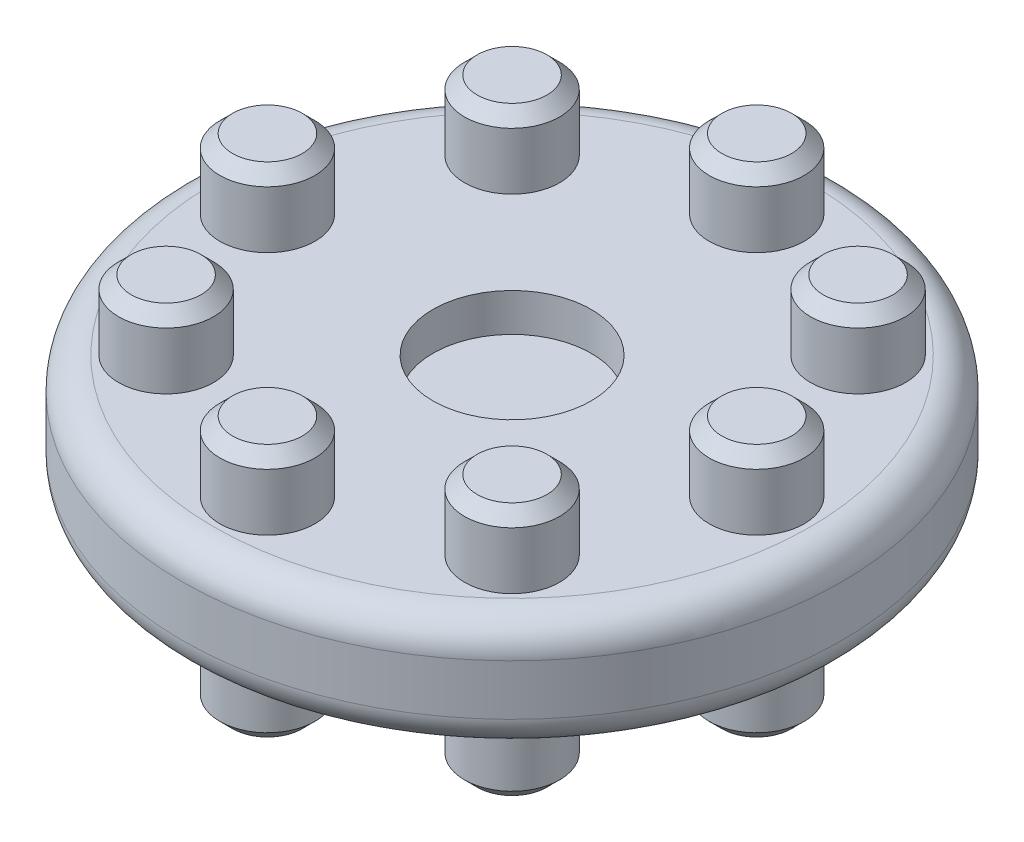
SolidWorks part; units mm, degrees
ref_plane "Front Plane" through (0, 0, 0) normal (0, 0, 1) x (1, 0, 0)
ref_plane "Top Plane" through (0, 0, 0) normal (0, 1, 0) x (1, 0, 0)
ref_plane "Right Plane" through (0, 0, 0) normal (1, 0, 0) x (0, 0, -1)
sketch "Sketch1" plane through (0, 0, 0) normal (0, 1, 0) x (1, 0, 0)
  circle A0 centre (0, 0) radius 26
  circle A1 centre (-13.6472, 13.6472) radius 3.75
  circle A2 centre (0, 19.3) radius 3.75
  circle A3 centre (13.6472, 13.6472) radius 3.75
  circle A4 centre (19.3, 0) radius 3.75
  circle A5 centre (13.6472, -13.6472) radius 3.75
  circle A6 centre (0, -19.3) radius 3.75
  circle A7 centre (-13.6472, -13.6472) radius 3.75
  circle A8 centre (-19.3, 0) radius 3.75
  circle A9 centre (0, 0) radius 6.25
  point P5 (0, 0)
  circle B0 centre (0, 19.3) radius 3.75
  circle B1 centre (13.6472, 13.6472) radius 3.75
  circle B2 centre (0, 0) radius 6.25
  circle B3 centre (-13.6472, 13.6472) radius 3.75
  circle B4 centre (-19.3, 0) radius 3.75
  circle B5 centre (-13.6472, -13.6472) radius 3.75
  circle B6 centre (0, -19.3) radius 3.75
  circle B7 centre (13.6472, -13.6472) radius 3.75
  circle B8 centre (19.3, 0) radius 3.75
sketch_block_instance "Block2-9"
sketch_block "Block2" parameters "D2"=3.9779, "D1"=8
extrude "Boss-Extrude1" add sketch "Sketch1" along normal blind 9 contours A0
sketch "Sketch2" plane through (0, 0, 0) normal (0, -1, 0) x (1, 0, 0)
  circle A1 centre (0, 0) radius 6.1
extrude "Cut-Extrude2" cut sketch "Sketch2" against normal blind 3
extrude "Cut-Extrude5" cut sketch "Sketch1<9>" against normal blind 3 from surface contours A9 starting at face at (0, 9, 26)
sketch "Sketch1<9>" plane through (0, 0, 0) normal (0, 1, 0) x (1, 0, 0) same geometry as "Sketch1"
extrude "Boss-Extrude3" add sketch "Sketch1<11>" against normal blind 5.5 contours A1 | A2 | A3 | A4 | A5 | A6 | A7 | A8
sketch "Sketch1<11>" plane through (0, 0, 0) normal (0, 1, 0) x (1, 0, 0) same geometry as "Sketch1"
extrude "Boss-Extrude4" add sketch "Sketch1<12>" along normal blind 5.5 from surface contours A4 | A3 | A2 | A1 | A6 | A5 | A8 | A7 starting at face at (0, 9, 6.25)
sketch "Sketch1<12>" plane through (0, 0, 0) normal (0, 1, 0) x (1, 0, 0) same geometry as "Sketch1"
chamfer "Chamfer1" distance 1 angle 45 16 edges at (13.6472, 14.5, -9.8972) (-19.3, -5.5, 3.75) (-13.6472, -5.5, 17.3972) (0, -5.5, 23.05) (13.6472, -5.5, 17.3972) (19.3, -5.5, 3.75) (13.6472, -5.5, -9.8972) (0, -5.5, -15.55) (-13.6472, -5.5, -9.8972) (-19.3, 14.5, 3.75) (-13.6472, 14.5, 17.3972) (0, 14.5, 23.05) (13.6472, 14.5, 17.3972) (19.3, 14.5, 3.75) (0, 14.5, -15.55) (-13.6472, 14.5, -9.8972)
fillet "Fillet1" radius 2.5 2 edges at (0, 0, 26) (0, 9, 26)
